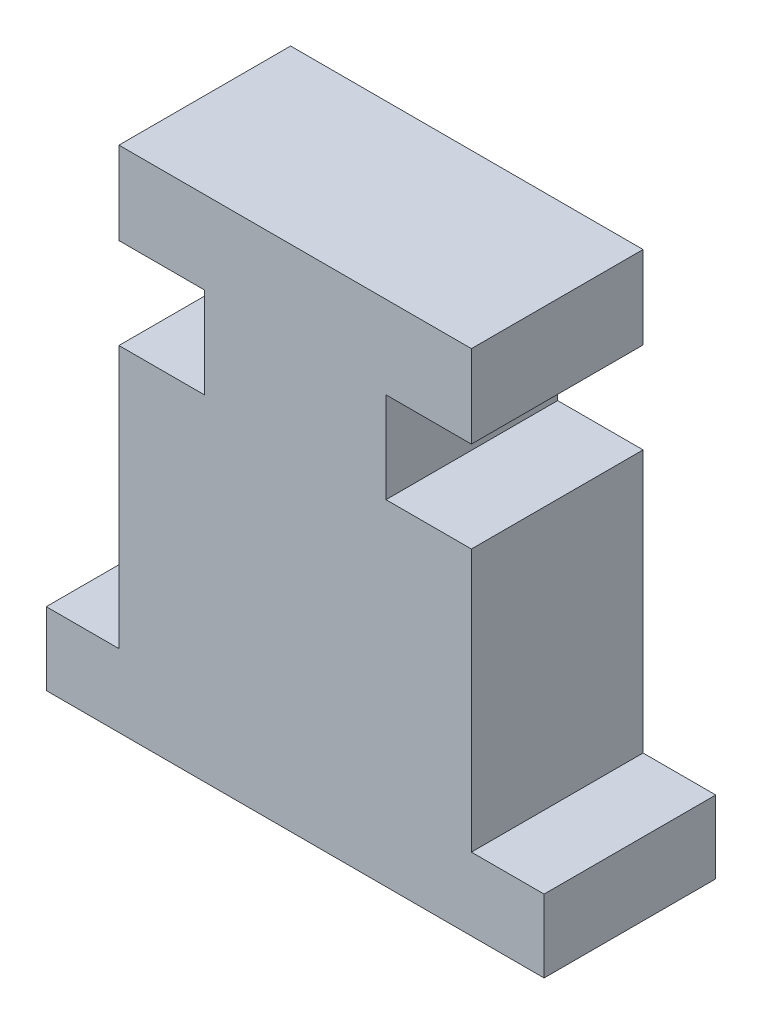
SolidWorks part; units mm, degrees
ref_plane "Front Plane" through (0, 0, 0) normal (0, 0, 1) x (1, 0, 0)
ref_plane "Top Plane" through (0, 0, 0) normal (0, 1, 0) x (1, 0, 0)
ref_plane "Right Plane" through (0, 0, 0) normal (1, 0, 0) x (0, 0, -1)
sketch "Sketch1" plane through (0, 0, 0) normal (0, 1, 0) x (1, 0, 0)
  line L0 (-8.6995, 5.54) -> (8.6995, 5.54)
  line L1 (-6.1595, 3) -> (6.1595, 3)
  line L2 (-6.1595, 3) -> (-6.1595, -3)
  line L3 (-6.1595, -3) -> (6.1595, -3)
  line L4 (6.1595, 3) -> (6.1595, -3)
  line L5 (8.6995, 5.54) -> (8.6995, -5.54)
  line L6 (-8.6995, -5.54) -> (8.6995, -5.54)
  line L7 (-8.6995, 5.54) -> (-8.6995, -5.54)
  line L8 (-8.6995, 3) -> (8.6995, 3)
  line L9 (-8.6995, -3) -> (8.6995, -3)
  point P4 (0, 3)
  point P6 (-6.1595, 0)
  dimension "D1" = 6
  dimension "D2" = 12.319
  dimension "D3" = 2.54
extrude "Boss-Extrude1" add sketch "Sketch1" along normal blind 15.24 contours L4 L1 L2 L3 region at (0, 0, 0)
extrude "Boss-Extrude2" add sketch "Sketch1<3>" against normal blind 2.54 contours L4 L1 L2 L3 | L4 L9 L5 L8 | L7 L9 L2 L8 region at (-7.4295, 0, 0) region at (7.4295, 0, 0) region at (0, 0, 0)
sketch "Sketch1<3>" plane through (0, 0, 0) normal (0, 1, 0) x (1, 0, 0) same geometry as "Sketch1"
sketch "Sketch2" plane through (0, 0, -3) normal (0, 0, -1) x (-1, 0, 0)
  line L0 (-6.1595, 15.24) -> (-6.1595, 0) construction
  line L1 (-6.1595, 12.35) -> (6.1595, 12.35)
  line L2 (-6.1595, 12.35) -> (-6.1595, 9.175)
  line L3 (-6.1595, 9.175) -> (6.1595, 9.175)
  line L4 (6.1595, 12.35) -> (6.1595, 9.175)
  line L5 (6.1595, 15.24) -> (6.1595, 0) construction
  line L6 (-3.175, 12.35) -> (3.175, 12.35)
  line L7 (-3.175, 12.35) -> (-3.175, 9.175)
  line L8 (-3.175, 9.175) -> (3.175, 9.175)
  line L9 (3.175, 12.35) -> (3.175, 9.175)
  line L10 (-6.1595, 0) -> (-8.6995, 0) construction
  line L11 (-3.175, 12.35) -> (3.175, 12.35)
  line L12 (-3.175, 12.35) -> (3.175, 9.175) construction
  line L13 (3.175, 12.35) -> (-3.175, 9.175) construction
  point P14 (0, 10.7625)
  line M11 (-6.1595, 15.24) -> (-6.1595, 0)
  line M17 (6.1595, 0) -> (6.1595, 15.24)
  dimension "D1" = 9.175
  dimension "D2" = 3.175
  dimension "D3" = 6.35
extrude "Cut-Extrude1" cut sketch "Sketch2" against normal through all contours L7 L1 L3 M11 | L1 L9 L3 M17 region at (4.6672, 10.7625, -3) region at (-4.6673, 10.7625, -3)
